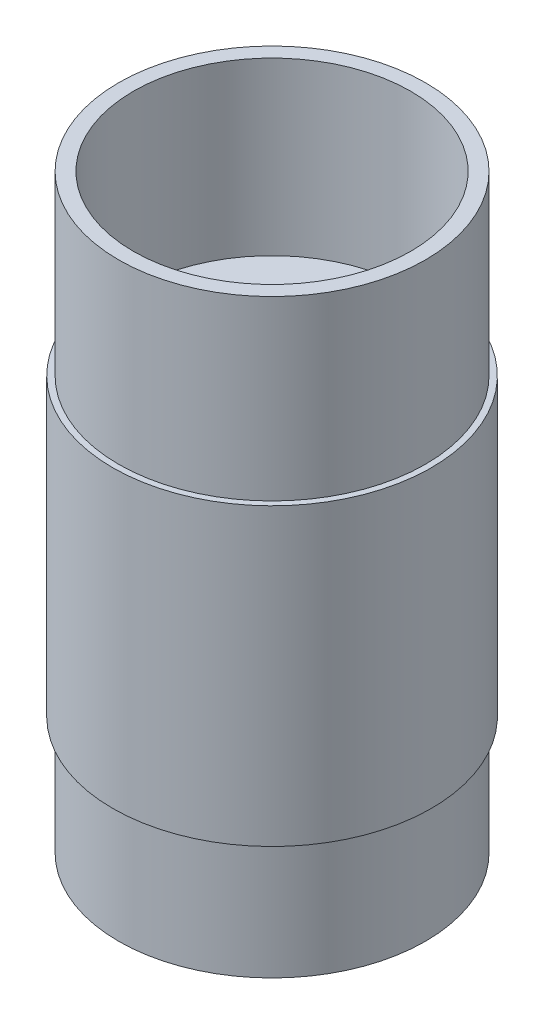
SolidWorks part; units mm, degrees
material "Balsa"
ref_plane "Plano frontal" through (0, 0, 0) normal (0, 0, 1) x (1, 0, 0)
ref_plane "Plano superior" through (0, 0, 0) normal (0, 1, 0) x (1, 0, 0)
ref_plane "Plano direito" through (0, 0, 0) normal (1, 0, 0) x (0, 0, -1)
sketch "Esboço1" plane through (0, 0, 0) normal (0, 1, 0) x (1, 0, 0)
  circle A0 centre (0, 0) radius 26
  circle A1 centre (0, 0) radius 23.5
extrude "Ressalto-extrusão1" add sketch "Esboço1" along normal blind 20 contours A1 | A0
sketch "Esboço2" plane through (0, 20, 0) normal (0, 1, 0) x (1, 0, 0)
  circle A0 centre (0, 0) radius 27
  circle A1 centre (0, 0) radius 25
extrude "Ressalto-extrusão2" add sketch "Esboço2" along normal blind 50 separate body contours A1 | A0
sketch "Esboço3" plane through (0, 70, 0) normal (0, 1, 0) x (1, 0, 0)
  circle A0 centre (0, 0) radius 23.5
  circle A1 centre (0, 0) radius 26
extrude "Ressalto-extrusão3" add sketch "Esboço3" along normal blind 30 separate body contours A1 | A0
sketch "Esboço18" plane through (0, 70, 0) normal (0, 1, 0) x (1, 0, 0)
  circle A0 centre (0, 0) radius 24
extrude "Ressalto-extrusão4" add sketch "Esboço18" along normal blind 1
